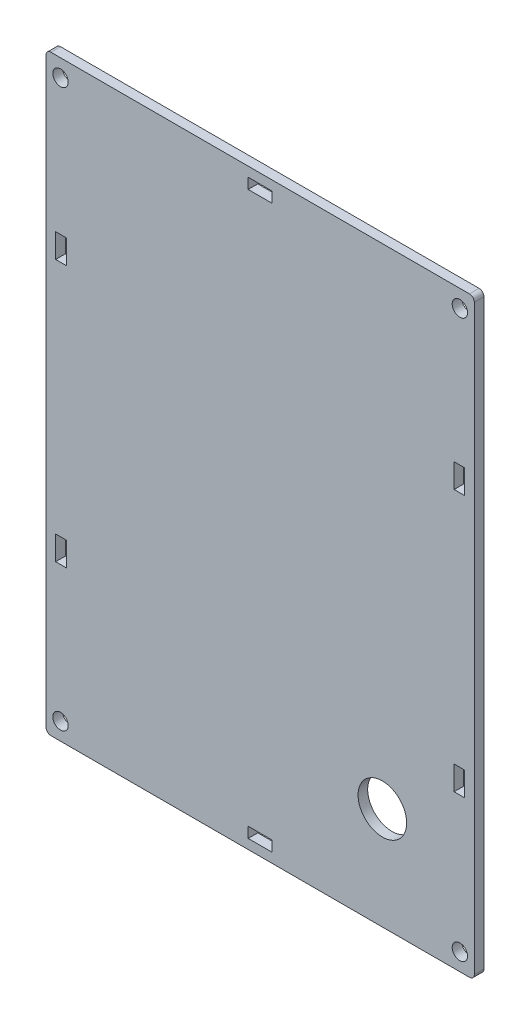
SolidWorks part; units mm, degrees
ref_plane "前基準面" through (0, 0, 0) normal (0, 0, 1) x (1, 0, 0)
ref_plane "上基準面" through (0, 0, 0) normal (0, 1, 0) x (1, 0, 0)
ref_plane "右基準面" through (0, 0, 0) normal (1, 0, 0) x (0, 0, -1)
sketch "Sketch1" plane through (0, 0, 0) normal (0, 0, 1) x (1, 0, 0)
  line L0 (0, 0) -> (-44.5, 0) construction
  line L1 (-44.5, 61.5) -> (44.5, 61.5)
  line L2 (-44.5, 61.5) -> (-44.5, -61.5)
  line L3 (-44.5, -61.5) -> (44.5, -61.5)
  line L4 (44.5, 61.5) -> (44.5, -61.5)
  line L5 (-44.5, 61.5) -> (44.5, -61.5) construction
  line L6 (-44.5, -61.5) -> (44.5, 61.5) construction
  line L7 (-44.5, 0) -> (44.5, 0) construction
  line L8 (0, 0) -> (0, -61.5) construction
  line L9 (0, -61.5) -> (0, 61.5) construction
  line L10 (-2.5, -57.3) -> (2.5, -57.3)
  line L11 (-2.5, 59.5) -> (2.5, 59.5)
  line L12 (-2.5, 59.5) -> (-2.5, 57.3)
  line L13 (-2.5, 57.3) -> (2.5, 57.3)
  line L14 (2.5, 59.5) -> (2.5, 57.3)
  line L15 (-2.5, 59.5) -> (2.5, 57.3) construction
  line L16 (-2.5, 57.3) -> (2.5, 59.5) construction
  line L17 (2.5, -59.5) -> (2.5, -57.3)
  line L18 (-2.5, -59.5) -> (2.5, -59.5)
  line L19 (-2.5, -59.5) -> (-2.5, -57.3)
  line L20 (-42.5, -24.7) -> (-40.3, -24.7)
  line L21 (-42.5, 29.7) -> (-40.3, 29.7)
  line L22 (-42.5, 29.7) -> (-42.5, 24.7)
  line L23 (-42.5, 24.7) -> (-40.3, 24.7)
  line L24 (-40.3, 29.7) -> (-40.3, 24.7)
  line L25 (-42.5, 29.7) -> (-40.3, 24.7) construction
  line L26 (-42.5, 24.7) -> (-40.3, 29.7) construction
  line L27 (-40.3, -29.7) -> (-40.3, -24.7)
  line L28 (-42.5, -29.7) -> (-40.3, -29.7)
  line L29 (-42.5, -29.7) -> (-42.5, -24.7)
  line L30 (42.5, -29.7) -> (42.5, -24.7)
  line L31 (42.5, -29.7) -> (40.3, -29.7)
  line L32 (40.3, -29.7) -> (40.3, -24.7)
  line L33 (42.5, -24.7) -> (40.3, -24.7)
  line L34 (42.5, 24.7) -> (40.3, 24.7)
  line L35 (40.3, 29.7) -> (40.3, 24.7)
  line L36 (42.5, 29.7) -> (40.3, 29.7)
  line L37 (42.5, 29.7) -> (42.5, 24.7)
  circle A0 centre (-41.5, 57.9) radius 1.6
  circle A1 centre (-41.5, -57.9) radius 1.6
  circle A2 centre (41.5, -57.9) radius 1.6
  circle A3 centre (41.5, 57.9) radius 1.6
  point P0 (0, 0)
  point P19 (0, 58.4)
  point P28 (-41.4, 27.2)
  dimension "D4" = 3.2
  dimension "D1" = 89
  dimension "D2" = 123
  dimension "D3" = 3.6
  dimension "D5" = 3
  dimension "D6" = 2
  dimension "D7" = 5
  dimension "D8" = 2.2
  dimension "D9" = 27.2
  dimension "D10" = 2
  dimension "D11" = 5
  dimension "D12" = 2.2
extrude "Boss-Extrude1" add sketch "Sketch1" along normal mid plane 2
fillet "Fillet1" radius 1 4 edges at (44.5, 61.5, 0) (44.5, -61.5, 0) (-44.5, -61.5, 0) (-44.5, 61.5, 0)
sketch "Sketch2" plane through (0, 0, 1) normal (0, 0, 1) x (1, 0, 0)
  line L0 (44.5, -60.5) -> (44.5, 60.5) construction
  line L1 (-43.5, -61.5) -> (43.5, -61.5) construction
  circle A0 centre (25.3901, -40.2537) radius 5.05
  dimension "D1" = 10.1
  dimension "D2" = 19.1099
  dimension "D3" = 21.2463
extrude "Cut-Extrude1" cut sketch "Sketch2" against normal up to next
